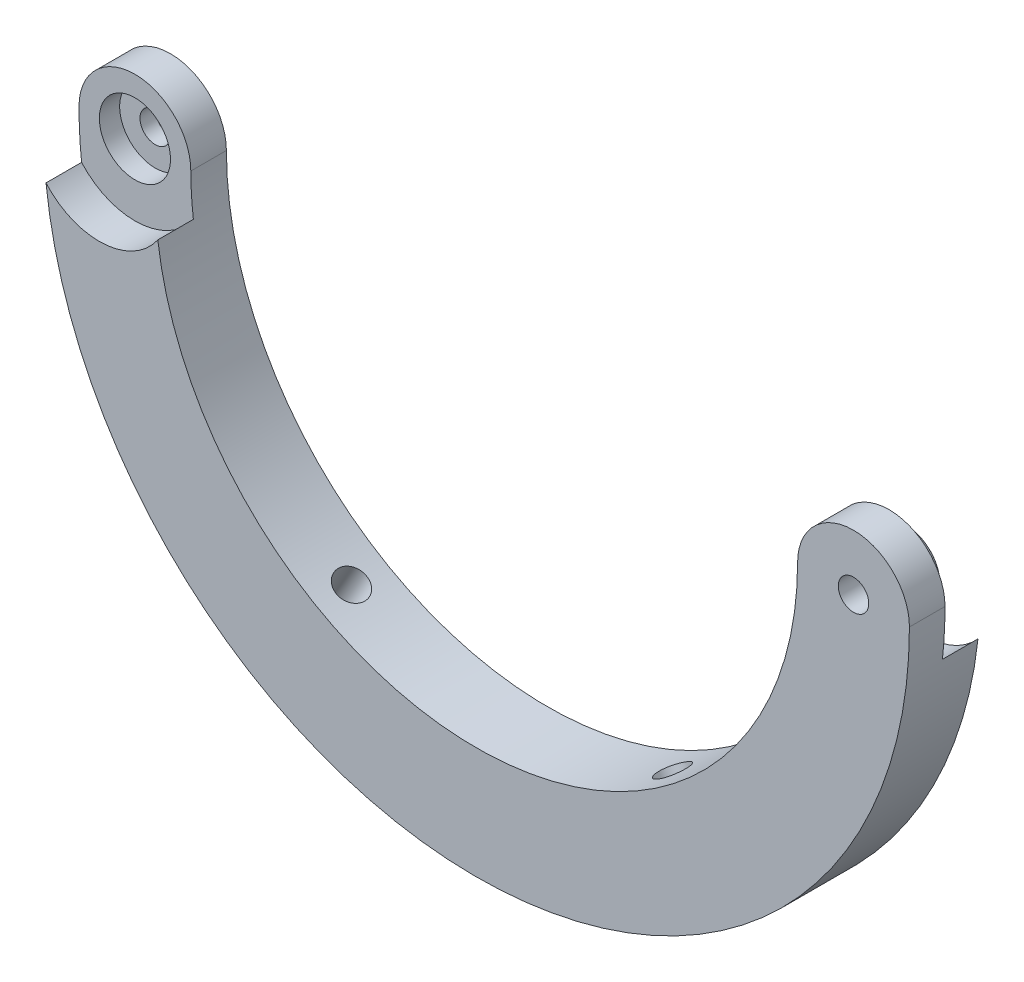
SolidWorks part; units mm, degrees
ref_plane "Front Plane" through (0, 0, 0) normal (0, 0, 1) x (1, 0, 0)
ref_plane "Top Plane" through (0, 0, 0) normal (0, 1, 0) x (1, 0, 0)
ref_plane "Right Plane" through (0, 0, 0) normal (1, 0, 0) x (0, 0, -1)
sketch "Sketch1" plane through (0, 0, 0) normal (0, 0, 1) x (1, 0, 0)
  line L0 (0, 0) -> (63.472, 0) construction
  line L3 (0, 0) -> (-24.3689, -42.2082) construction
  line L4 (0, 0) -> (22.1531, -38.3703) construction
  circle A0 centre (0, 0) radius 31.6 construction
  arc A1 (-31.6, 0) -> (31.6, 0) centre (0, 0) ccw
  arc A2 (-42.6, 0) -> (42.6, 0) centre (0, 0) ccw
  arc A3 (-31.6, 0) -> (-42.6, 0) centre (-37.1, 0) ccw
  circle A4 centre (0, 0) radius 31.6 construction
  circle A5 centre (0, 0) radius 42.6 construction
  arc A6 (42.6, 0) -> (31.6, 0) centre (37.1, 0) ccw
  point P4 (37.6, 0)
  point P12 (30.2192, 9.2389)
  point P19 (-21.3, -36.8927)
  dimension "D1" = 11
extrude "Boss-Extrude1" add sketch "Sketch1" along normal mid plane 7
ref_plane "Plane1" through (-21.3, -36.8927, 0) normal (-0.5, -0.866, 0) x (-0.866, 0.5, 0)
sketch "Sketch8" plane through (-21.3, -36.8927, 0) normal (-0.5, -0.866, 0) x (-0.866, 0.5, 0)
  circle A0 centre (0, 0) radius 1.5
extrude "Cut-Extrude7" cut sketch "Sketch8" against normal through all
sketch "Sketch9" plane through (-21.3, -36.8927, 0) normal (-0.5, -0.866, 0) x (-0.866, 0.5, 0)
  circle A0 centre (0, 0) radius 3
extrude "Cut-Extrude8" cut sketch "Sketch9" against normal blind 7
mirror "Mirror1" about plane through (0, 0, 0) normal (1, 0, 0) of "Cut-Extrude7", "Cut-Extrude8"
sketch "Sketch10" plane through (0, 0, 0) normal (0, 0, 1) x (1, 0, 0)
  circle A0 centre (-37.1, 0) radius 7
  circle A1 centre (37.1, 0) radius 7
extrude "Cut-Extrude9" cut sketch "Sketch10" along normal through all contours A0
extrude "Cut-Extrude10" cut sketch "Sketch10<3>" against normal through all contours A1
sketch "Sketch10<3>" plane through (0, 0, 0) normal (0, 0, 1) x (1, 0, 0) same geometry as "Sketch10"
sketch "Sketch11" plane through (0, 0, 0) normal (0, 0, 1) x (1, 0, 0)
  circle A0 centre (-37.1, 0) radius 3.5
extrude "Cut-Extrude11" cut sketch "Sketch11" against normal blind 2 contours A0
sketch "Sketch12" plane through (0, 0, -2) normal (0, 0, 1) x (1, 0, 0)
  circle A0 centre (-37.1, 0) radius 1.5
extrude "Cut-Extrude12" cut sketch "Sketch12" against normal through all
sketch "Sketch13" plane through (0, 0, 0) normal (0, 0, -1) x (-1, 0, 0)
  circle A0 centre (-37.1, 0) radius 3.5
extrude "Boss-Extrude3" add sketch "Sketch13" along normal blind 1.8 contours A0
sketch "Sketch14" plane through (0, 0, -1.8) normal (0, 0, -1) x (-1, 0, 0)
  circle A0 centre (-37.1, 0) radius 1.5
extrude "Cut-Extrude13" cut sketch "Sketch14" against normal through all
fillet "Fillet1" radius 0.5 1 edges at (33.6, 0, -1.8)
